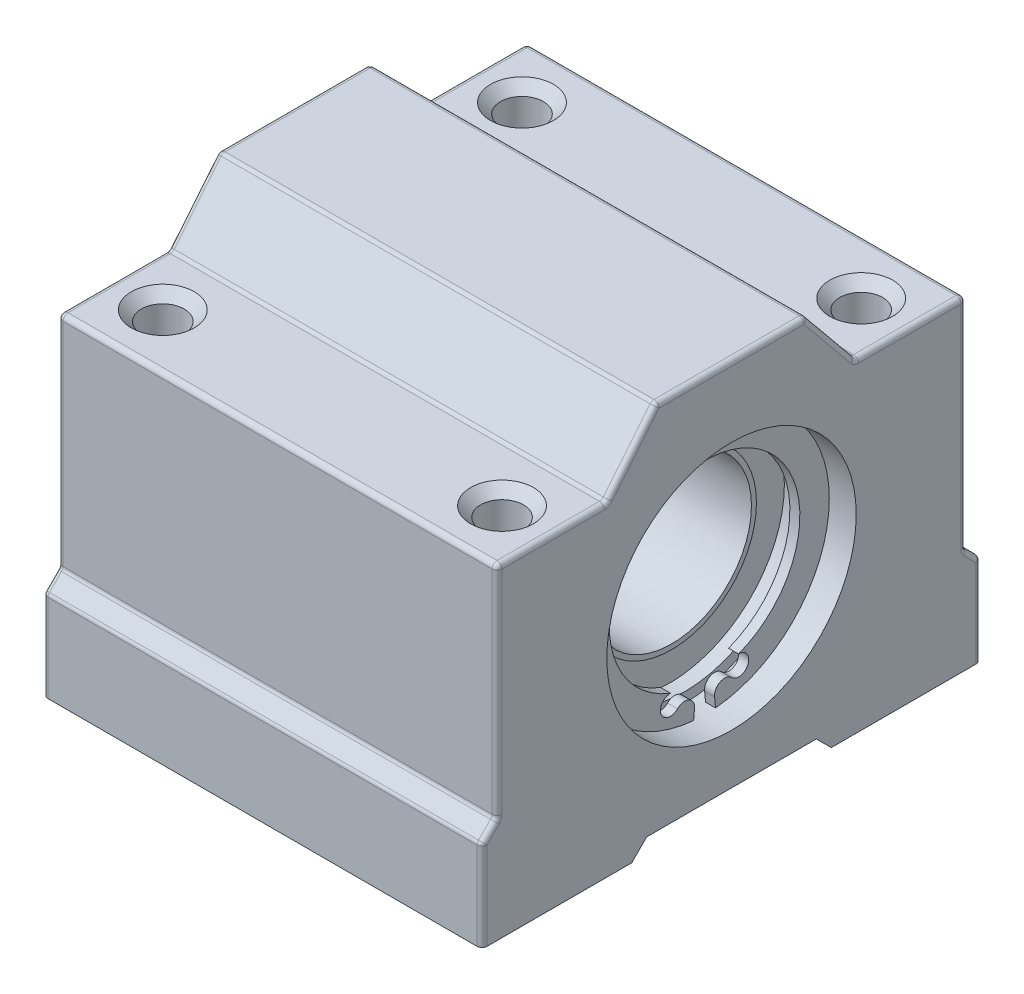
SolidWorks part; units mm, degrees
ref_plane "Front Plane" through (0, 0, 0) normal (0, 0, 1) x (1, 0, 0)
ref_plane "Top Plane" through (0, 0, 0) normal (0, 1, 0) x (1, 0, 0)
ref_plane "Right Plane" through (0, 0, 0) normal (1, 0, 0) x (0, 0, -1)
sketch "Sketch1" plane through (0, 0, 0) normal (1, 0, 0) x (0, 0, -1)
  line L1 (-10, -19) -> (-8.5, -17.5)
  line L2 (-8.5, -17.5) -> (8.5, -17.5)
  line L3 (8.5, -17.5) -> (10, -19)
  line L4 (10, -19) -> (25, -19)
  line L6 (25, -10) -> (23.5, -8.5)
  line L8 (23.5, 13.5) -> (12.5, 13.5)
  line L9 (12.5, 13.5) -> (7.5, 19.6)
  line L10 (7.5, 19.6) -> (-7.5, 19.6)
  line L11 (-7.5, 19.6) -> (-12.5, 13.5)
  line L12 (-12.5, 13.5) -> (-23.5, 13.5)
  line L15 (-25, -10) -> (-25, -19)
  line L16 (0, -17.5) -> (0, 19.6) construction
  line L17 (-16.278, 0) -> (14.0247, 0) construction
  line L18 (-25, -19) -> (-10, -19)
  line L19 (25, -10) -> (25, -19)
  line L20 (-23.5, -8.5) -> (-23.5, 13.5)
  line L21 (23.5, -8.5) -> (23.5, 13.5)
  line L22 (-18, 13.5) -> (-18, -19) construction
  line L23 (-18, -19) -> (18, 13.5) construction
  line L24 (18, 13.5) -> (18, -19) construction
  line L25 (-25, -10) -> (-23.5, -8.5)
  line L26 (-12.5, 0) -> (12.5, 0) construction
  circle A0 centre (0, 0) radius 12.5
  circle A1 centre (0, 0) radius 11.5
  circle A2 centre (0, 0) radius 8
  point P18 (0, 19.6)
  point P23 (0, 0)
  dimension "D12" = 16
  dimension "D1" = 50
  dimension "D2" = 32.5
  dimension "D3" = 19
  dimension "D5" = 38.6
  dimension "D6" = 36
  dimension "D4" = 9
  dimension "D7" = 1.5
  dimension "D8" = 15
  dimension "D9" = 1.5
  dimension "D10" = 15
  dimension "D11" = 1
extrude "Boss-Extrude1" add sketch "Sketch1" along normal blind 44 contours L25 L15 L18 L1 L2 L3 L4 L19 L6 L21 L8 L9 L10 L11 L12 L20 A0 region at (0, -18.3683, 17.5)
extrude "Extrude-Thin1" add sketch "Sketch1<4>" along normal blind 37.5 from offset 0.5 separate body thin contours A2 thin type one direction wall 0.5
sketch "Sketch1<4>" plane through (0, 0, 0) normal (1, 0, 0) x (0, 0, -1) same geometry as "Sketch1"
extrude "Boss-Extrude2" add sketch "Sketch1<5>" along normal blind 37 from offset 0.8 contours A1 A2 region at (0, 0, 11.1747)
sketch "Sketch1<5>" plane through (0, 0, 0) normal (1, 0, 0) x (0, 0, -1) same geometry as "Sketch1"
extrude "Boss-Extrude3" add sketch "Sketch1<6>" along normal blind 39 from offset 0.3 contours A0 A1 region at (0, 0, 12.1464)
sketch "Sketch1<6>" plane through (0, 0, 0) normal (1, 0, 0) x (0, 0, -1) same geometry as "Sketch1"
ref_plane "Plane1" through (39.3, 0, 0) normal (1, 0, 0) x (0, 0, -1)
sketch "Sketch3" plane through (39.3, 0, 0) normal (1, 0, 0) x (0, 0, -1)
  line L0 (0, 0) -> (0, -50000) construction
  line L1 (-1.0086, -11.4557) -> (-1.0963, -12.4518)
  line L2 (1.0086, -11.4557) -> (1.0963, -12.4518)
  circle A0 centre (0, 0) radius 12.5 construction
  arc A1 (1.0963, -12.4518) -> (-1.0963, -12.4518) centre (0, 0) ccw
  circle A2 centre (0, 0) radius 11.5 construction
  arc A3 (0, -11.5) -> (1.0086, -11.4557) centre (0, 0) ccw
  arc A4 (-1.0086, -11.4557) -> (-2.7141, -10.6247) centre (-2, -11.3248) ccw
  circle A5 centre (-2, -11.3248) radius 0.25
  arc A6 (-2.2457, -11.2786) -> (-1.7534, -11.3656) centre (0, 0) ccw
  arc A7 (-2.7141, -10.6247) -> (-3.4089, -8.9248) centre (-3.4281, -9.9246) cw
  arc A8 (2.7141, -10.6247) -> (3.4089, -8.9248) centre (3.4281, -9.9246) ccw
  circle A10 centre (2, -11.3248) radius 0.25
  arc A11 (1.0086, -11.4557) -> (2.7141, -10.6247) centre (2, -11.3248) cw
  arc A13 (3.4089, -8.9248) -> (-3.4089, -8.9248) centre (0, 0) ccw
  point P12 (-1.1793, -6.3921)
  dimension "D1" = 0.5
  dimension "D2" = 2
  dimension "D3" = 1
  dimension "D4" = 2
extrude "Boss-Extrude4" add sketch "Sketch3" along normal blind 1 from offset 1 contours A11 A8 A13 A7 A4 L1 A1 L2
fillet "Fillet1" radius 0.5 32 edges at (22, -8.5, -23.5) (22, -8.5, 23.5) (22, -10, 25) (22, -10, -25) (22, 13.5, -12.5) (22, 13.5, 12.5) (22, 19.6, 7.5) (22, 19.6, -7.5) (22, 13.5, -23.5) (22, 13.5, 23.5) (44, 16.55, -10) (44, 16.55, 10) (44, 2.5, 23.5) (0, -9.25, 24.25) (0, 16.55, 10) (44, -9.25, -24.25) (44, -14.5, -25) (44, 2.5, -23.5) (44, 19.6, 0) (44, 13.5, -18) (44, 13.5, 18) (44, -9.25, 24.25) (44, -14.5, 25) (0, -14.5, -25) (0, -9.25, -24.25) (0, 2.5, -23.5) (0, 16.55, -10) (0, 13.5, -18) (0, 19.6, 0) (0, -14.5, 25) (0, 2.5, 23.5) (0, 13.5, 18)
sketch "Sketch4" plane through (0, -19, 0) normal (0, -1, 0) x (1, 0, 0)
  line L0 (22, 25) -> (22, -25) construction
  line L1 (43.5, 25) -> (0.5, 25) construction
  line L2 (43.5, -25) -> (0.5, -25) construction
  line L4 (-4.9444, 18) -> (27.0918, 18) construction
  line L6 (0, 0) -> (36.1646, 0) construction
  circle A0 centre (5, 18) radius 2.15
  circle A1 centre (39, 18) radius 2.15
  circle A2 centre (39, -18) radius 2.15
  circle A3 centre (5, -18) radius 2.15
  dimension "D2" = 4.3
  dimension "D1" = 18
  dimension "D3" = 34
extrude "Cut-Extrude3" cut sketch "Sketch4" against normal through all
chamfer "Chamfer1" distance 1 angle 45 6 edges at (39, 13.5, -20.15) (5, 13.5, -20.15) (5, 13.5, 15.85) (39, 13.5, 15.85) (39, -19, 20.15) (5, -19, 15.85)
equation "\"D1@Boss-Extrude2\"= \"D1@Boss-Extrude1\" - 2 - 5"
equation "\"D1@Boss-Extrude3\"= \"D1@Boss-Extrude1\" - 5"
equation "\"D1@Sketch4\"= \"D6@Sketch1\" / 2"
equation "\"D1@Extrude-Thin1\"= \"D1@Boss-Extrude3\" - 1.5"
